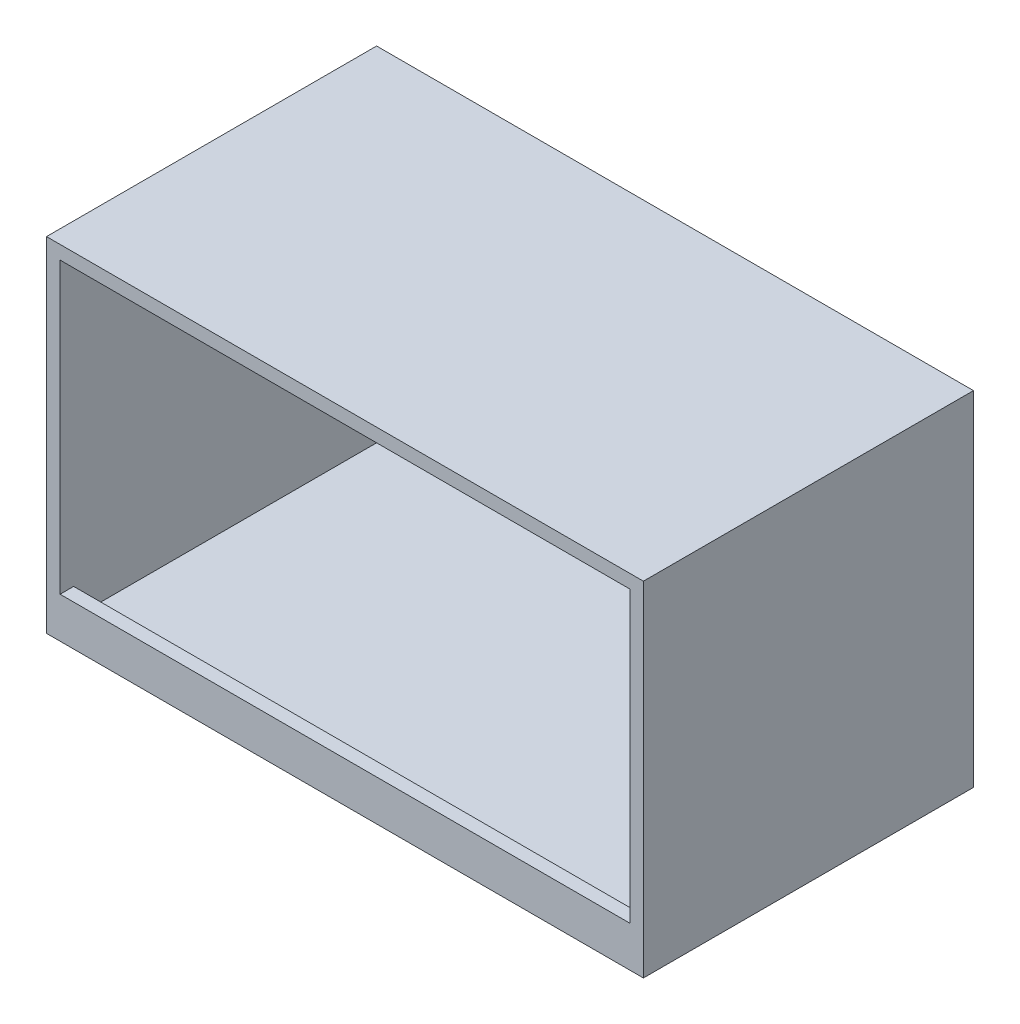
SolidWorks part; units mm, degrees
ref_plane "前视基准面" through (0, 0, 0) normal (0, 0, 1) x (1, 0, 0)
ref_plane "上视基准面" through (0, 0, 0) normal (0, 1, 0) x (1, 0, 0)
ref_plane "右视基准面" through (0, 0, 0) normal (1, 0, 0) x (0, 0, -1)
sketch "草图1" plane through (0, 0, 0) normal (0, 0, 1) x (1, 0, 0)
  line L1 (0, 0) -> (66, 0)
  line L2 (0, 0) -> (0, -38)
  line L3 (0, -38) -> (66, -38)
  line L4 (66, 0) -> (66, -38)
  dimension "D1" = 66
  dimension "D2" = 38
extrude "凸台-拉伸1" add sketch "草图1" along normal blind 1.5
sketch "草图2" plane through (0, 0, 1.5) normal (0, 0, 1) x (1, 0, 0)
  line L0 (64.5, -36.5) -> (64.5, -1.5)
  line L1 (66, -38) -> (0, -38)
  line L2 (66, -38) -> (66, 0)
  line L3 (66, 0) -> (0, 0)
  line L4 (0, -38) -> (0, 0)
  line L5 (64.5, -1.5) -> (1.5, -1.5)
  line L6 (1.5, -36.5) -> (1.5, -1.5)
  line L7 (64.5, -36.5) -> (1.5, -36.5)
  dimension "D1" = 1.5
extrude "凸台-拉伸2" add sketch "草图2" along normal blind 35
sketch "草图3" plane through (0, -36.5, 0) normal (0, 1, 0) x (1, 0, 0)
  line L0 (64.5, -36.5) -> (64.5, -1.5) construction
  line L1 (1.5, -36.5) -> (64.5, -36.5)
  line L2 (1.5, -36.5) -> (1.5, -35)
  line L3 (1.5, -35) -> (64.5, -35)
  line L4 (64.5, -36.5) -> (64.5, -35)
  dimension "D1" = 1.5
extrude "凸台-拉伸3" add sketch "草图3" along normal blind 3
fillet "圆角1" radius 3 1 edges at (33, -36.5, 35)
